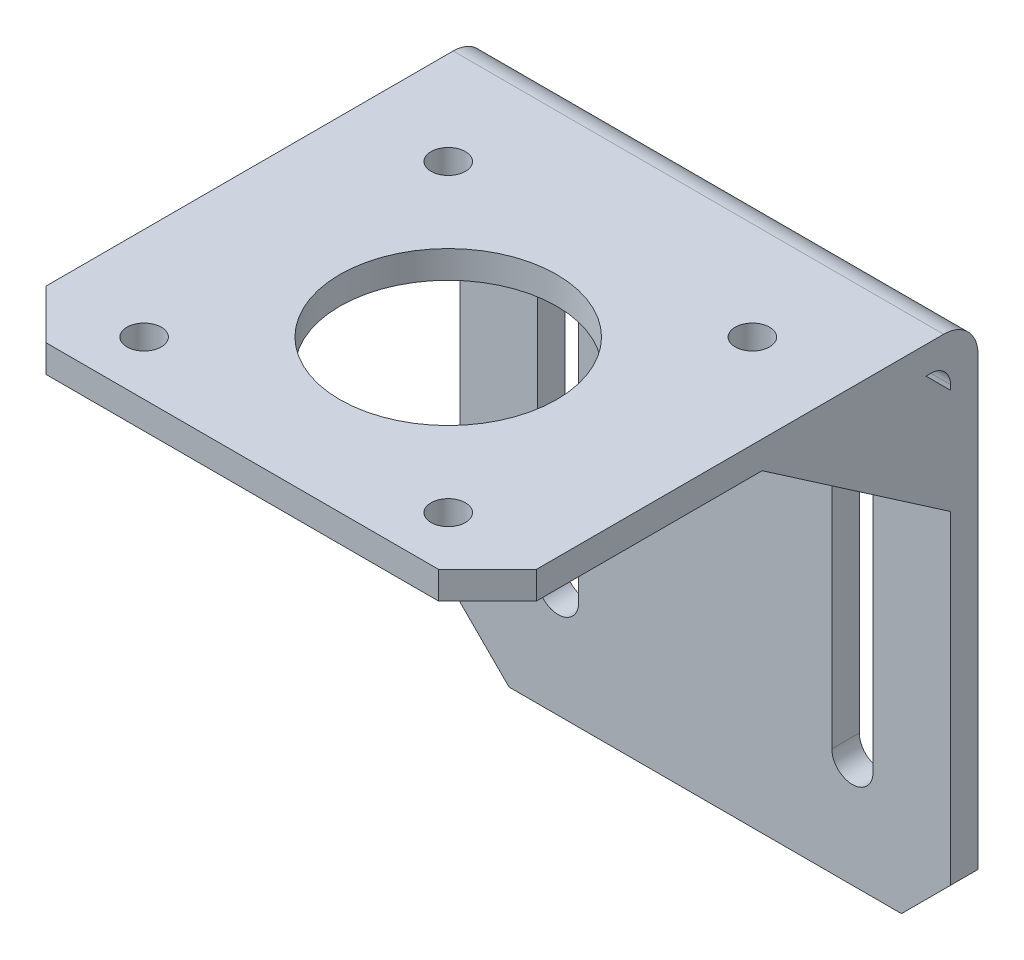
SolidWorks part; units mm, degrees
ref_plane "Front Plane" through (0, 0, 0) normal (0, 0, 1) x (1, 0, 0)
ref_plane "Top Plane" through (0, 0, 0) normal (0, 1, 0) x (1, 0, 0)
ref_plane "Right Plane" through (0, 0, 0) normal (1, 0, 0) x (0, 0, -1)
sketch "Sketch1" plane through (0, 0, 0) normal (1, 0, 0) x (0, 0, -1)
  line L0 (-50, 0) -> (-50, -2.8)
  line L1 (-50, -2.8) -> (-2.8, -2.8)
  line L2 (-2.8, -2.8) -> (-2.8, -54)
  line L3 (-2.8, -54) -> (0, -54)
  line L4 (0, -54) -> (0, 0)
  line L5 (0, 0) -> (-50, 0)
  point P2 (0, 0)
  point P8 (5.2571, 2.8)
  point P9 (-23.0857, 2.8)
  point P10 (0, 0)
  point P11 (0, 0)
  dimension "D1" = 2.8
  dimension "D2" = 2.8
  dimension "D3" = 50
  dimension "D4" = 54
extrude "Boss-Extrude1" add sketch "Sketch1" along normal blind 25 and the other way blind 25
sketch "Sketch3" plane through (0, 0, 0) normal (0, 1, 0) x (1, 0, 0)
  line L0 (0, 0) -> (0, -50) construction
  line L1 (-25, -50) -> (25, -50) construction
  line L3 (-15.5, -44.5) -> (15.5, -44.5) construction
  line L4 (-15.5, -44.5) -> (-15.5, -13.5) construction
  line L5 (-15.5, -13.5) -> (15.5, -13.5) construction
  line L6 (15.5, -44.5) -> (15.5, -13.5) construction
  line L7 (-15.5, -44.5) -> (15.5, -13.5) construction
  line L8 (-15.5, -13.5) -> (15.5, -44.5) construction
  circle A0 centre (0, -29) radius 11.05
  circle A1 centre (-15.5, -13.5) radius 1.75
  circle A2 centre (15.5, -13.5) radius 1.75
  circle A3 centre (15.5, -44.5) radius 1.75
  circle A4 centre (-15.5, -44.5) radius 1.75
  point P15 (0, -40.05)
  dimension "D2" = 22.1
  dimension "D4" = 3.5
  dimension "D5" = 3.5
  dimension "D6" = 3.5
  dimension "D7" = 3.5
  dimension "D3" = 31
  dimension "D1" = 21
extrude "Cut-Extrude1" cut sketch "Sketch3" against normal through all
sketch "Sketch4" plane through (0, 0, 0) normal (0, 0, -1) x (-1, 0, 0)
  line L0 (-15, 0) -> (-15, -54) construction
  line L1 (25, 0) -> (-25, 0) construction
  line L2 (25, -54) -> (-25, -54) construction
  line L3 (15, 0) -> (15, -54) construction
  line L4 (-15, -43) -> (-15, -13) construction
  line L5 (-17.1, -43) -> (-17.1, -13)
  line L6 (-12.9, -43) -> (-12.9, -13)
  line L7 (15, -43) -> (15, -13) construction
  line L8 (12.9, -43) -> (12.9, -13)
  line L9 (17.1, -43) -> (17.1, -13)
  line L10 (-15, -13) -> (15, -13) construction
  line L11 (-15, -43) -> (15, -43) construction
  arc A0 (-17.1, -43) -> (-12.9, -43) centre (-15, -43) ccw
  arc A1 (-12.9, -13) -> (-17.1, -13) centre (-15, -13) ccw
  arc A2 (12.9, -43) -> (17.1, -43) centre (15, -43) ccw
  arc A3 (17.1, -13) -> (12.9, -13) centre (15, -13) ccw
  point P11 (-15, -28)
  point P18 (15, -28)
  dimension "D1" = 15
  dimension "D2" = 15
  dimension "D3" = 4.2
  dimension "D4" = 4.2
  dimension "D5" = 30
  dimension "D6" = 11
extrude "Cut-Extrude2" cut sketch "Sketch4" against normal through all
chamfer "Chamfer1" distance 5 angle 45 4 edges at (25, -54, 1.4) (-25, -54, 1.4) (-25, -1.4, 50) (25, -1.4, 50)
fillet "Fillet1" radius 2 1 edges at (0, -2.8, 2.8)
fillet "Fillet2" radius 3.5 1 edges at (0, 0, 0)
sketch "Sketch5" plane through (-25, 0, 0) normal (-1, 0, 0) x (0, 0, 1)
  line L0 (2.8, -5.3) -> (5.3, -2.8)
  line L1 (2.8, -4.8) -> (2.8, -49) construction
  line L2 (45, -2.8) -> (4.8, -2.8) construction
  line L3 (5.3, -2.8) -> (22, -2.8)
  line L4 (22, -2.8) -> (2.8, -16)
  line L5 (2.8, -16) -> (2.8, -5.3)
  line L6 (0, -49) -> (0, -3.5) construction
  line L7 (3.5, 0) -> (45, 0) construction
  dimension "D1" = 45
  dimension "D2" = 0.5
  dimension "D3" = 22
  dimension "D4" = 16
extrude "Boss-Extrude2" add sketch "Sketch5" against normal blind 2.5
mirror "Mirror1" about plane through (0, 0, 0) normal (1, 0, 0) of "Boss-Extrude2"
equation "\"D5@Sketch3\"=\"D4@Sketch3\""
equation "\"D6@Sketch3\"=\"D4@Sketch3\""
equation "\"D7@Sketch3\"=\"D4@Sketch3\""
equation "\"D4@Sketch4\"=\"D3@Sketch4\""
